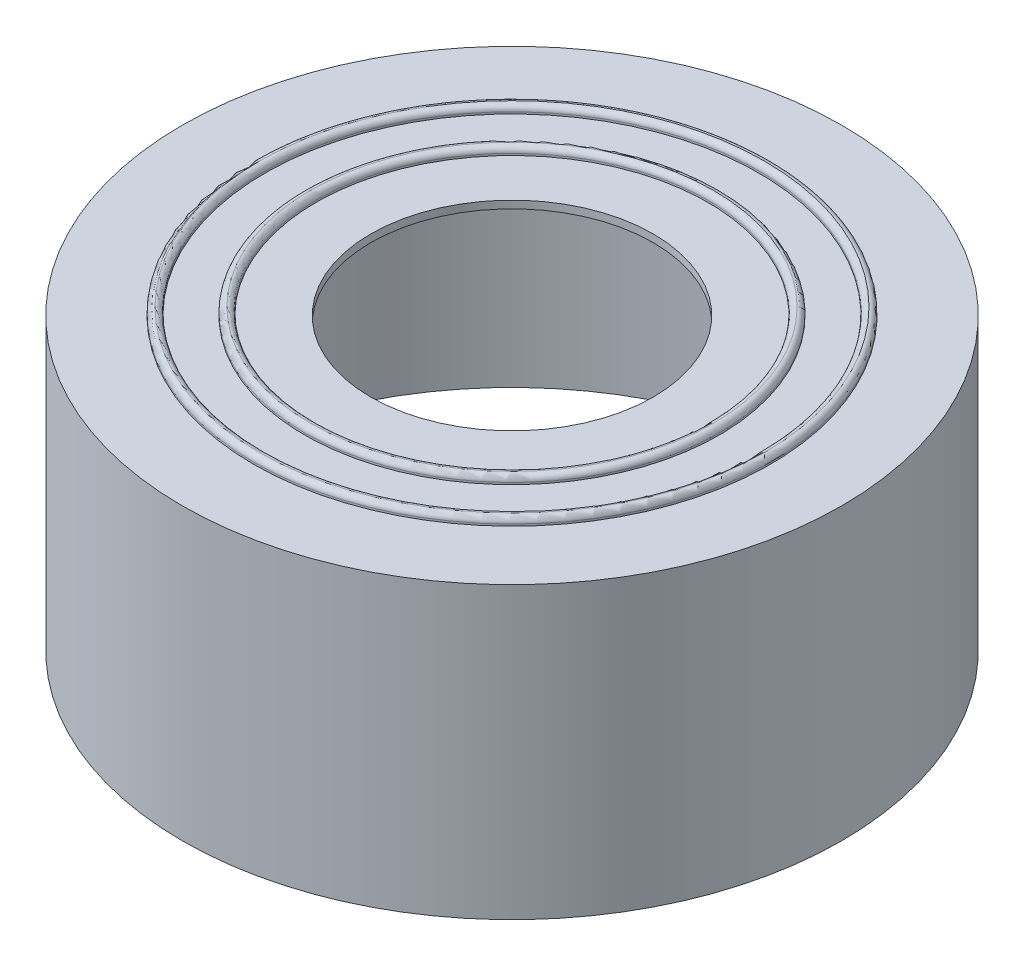
SolidWorks part; units mm, degrees
ref_plane "前视基准面" through (0, 0, 0) normal (0, 0, 1) x (1, 0, 0)
ref_plane "上视基准面" through (0, 0, 0) normal (0, 1, 0) x (1, 0, 0)
ref_plane "右视基准面" through (0, 0, 0) normal (1, 0, 0) x (0, 0, -1)
sketch "草图1" plane through (0, 0, 0) normal (0, 1, 0) x (1, 0, 0)
  circle A0 centre (0, 0) radius 55
  circle A1 centre (0, 0) radius 65.5
  circle A2 centre (0, 0) radius 52
  circle A3 centre (0, 0) radius 68.5
  dimension "D1" = 110
  dimension "D2" = 131
  dimension "D3" = 104
  dimension "D4" = 137
extrude "凸台-拉伸1" add sketch "草图1" along normal blind 2 contours A3 A1 | A0 A2 region at (-53.4444, 0, 0) region at (-66.5625, 0, 0)
sketch "草图2" plane through (0, 0, 0) normal (0, -1, 0) x (1, 0, 0)
  circle A0 centre (0, 0) radius 37.5
  circle A1 centre (0, 0) radius 87.5
  dimension "D1" = 175
  dimension "D2" = 75
extrude "凸台-拉伸2" add sketch "草图2" along normal blind 2
sketch "草图3" plane through (0, -2, 0) normal (0, -1, 0) x (1, 0, 0)
  circle A0 centre (0, 0) radius 87.5
  circle A1 centre (0, 0) radius 85.5
  circle A2 centre (0, 0) radius 87.5 construction
  dimension "D2" = 171
extrude "凸台-拉伸3" add sketch "草图3" along normal blind 75
fillet "圆角1" radius 1.5 4 edges at (0, 2, 52) (0, 2, 55) (0, 2, 65.5) (0, 2, 68.5)
